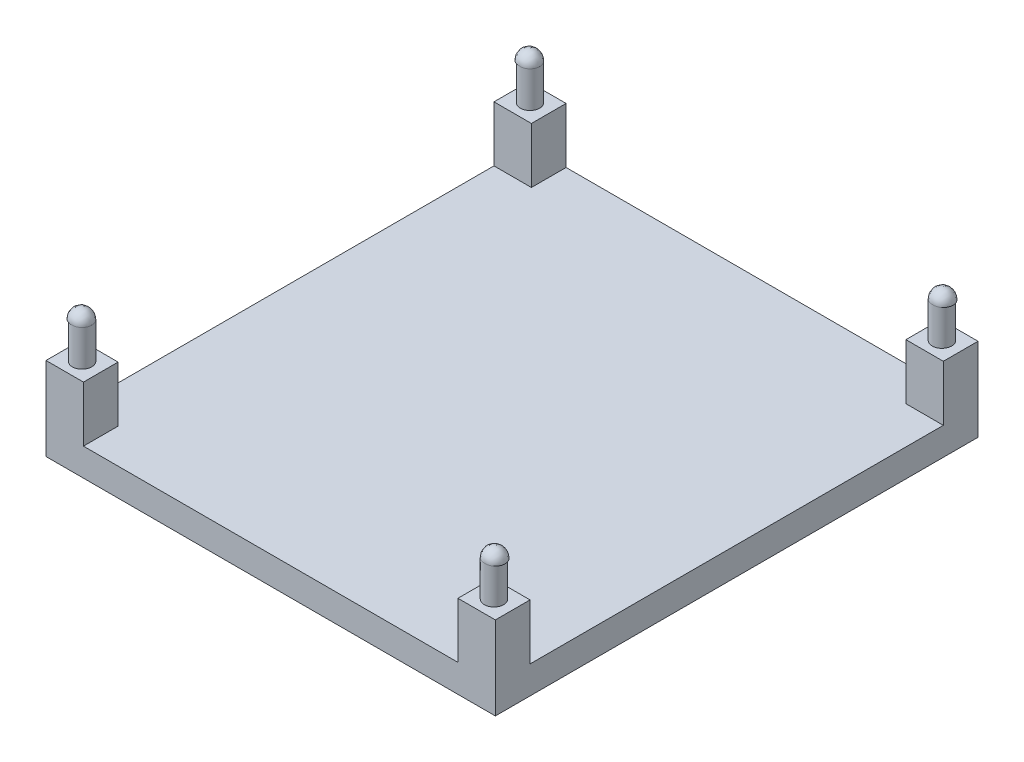
SolidWorks part; units mm, degrees
ref_plane "Front Plane" through (0, 0, 0) normal (0, 0, 1) x (1, 0, 0)
ref_plane "Top Plane" through (0, 0, 0) normal (0, 1, 0) x (1, 0, 0)
ref_plane "Right Plane" through (0, 0, 0) normal (1, 0, 0) x (0, 0, -1)
sketch "Sketch1" plane through (0, 0, 0) normal (0, 1, 0) x (1, 0, 0)
  line L0 (0, -44.45) -> (0, 44.45) construction
  line L1 (-41.275, 44.45) -> (41.275, 44.45)
  line L2 (-41.275, 44.45) -> (-41.275, -44.45)
  line L3 (-41.275, -44.45) -> (41.275, -44.45)
  line L4 (41.275, 44.45) -> (41.275, -44.45)
  line L5 (-41.275, 44.45) -> (41.275, -44.45) construction
  line L6 (-41.275, -44.45) -> (41.275, 44.45) construction
  line L7 (-41.275, 0) -> (41.275, 0) construction
  circle A0 centre (38.1, -41.275) radius 2.3812
  circle A1 centre (-38.1, -41.275) radius 2.3812
  circle A2 centre (38.1, 41.275) radius 2.3812
  circle A3 centre (-38.1, 41.275) radius 2.3812
  point P0 (0, 0)
  dimension "D3" = 76.2
  dimension "D5" = 38.1
  dimension "D6" = 3.175
  dimension "D1" = 88.9
  dimension "D2" = 82.55
  dimension "D4" = 82.55
sketch "Sketch2" plane through (0, 0, 0) normal (0, 1, 0) x (1, 0, 0)
  line L0 (0, -44.196) -> (0, 44.196) construction
  line L1 (-41.148, 44.196) -> (41.148, 44.196)
  line L2 (-41.148, 44.196) -> (-41.148, -44.196)
  line L3 (-41.148, -44.196) -> (41.148, -44.196)
  line L4 (41.148, 44.196) -> (41.148, -44.196)
  line L5 (-41.148, 44.196) -> (41.148, -44.196) construction
  line L6 (-41.148, -44.196) -> (41.148, 44.196) construction
  line L7 (-41.148, 0) -> (41.148, 0) construction
  circle A0 centre (37.719, -41.021) radius 1.778
  circle A1 centre (-37.719, -41.021) radius 1.778
  circle A2 centre (37.719, 41.021) radius 1.778
  circle A3 centre (-37.719, 41.021) radius 1.778
  point P0 (0, 0)
  dimension "D3" = 75.438
  dimension "D5" = 37.719
  dimension "D6" = 3.429
  dimension "D9" = 3.556
  dimension "D10" = 3.556
  dimension "D11" = 3.556
  dimension "D12" = 3.556
  dimension "D1" = 88.392
  dimension "D2" = 82.296
  dimension "D4" = 82.042
  dimension "D13" = 3.429
  dimension "D14" = 3.175
  dimension "D15" = 3.429
  dimension "D16" = 3.175
  dimension "D17" = 3.429
  dimension "D18" = 3.175
extrude "Boss-Extrude2" add sketch "Sketch2" along normal blind 21.844 contours A2 | A3 | A1 | A0
extrude "Boss-Extrude3" add sketch "Sketch2<4>" along normal blind 5.08 contours L2 L1 L4 L3
sketch "Sketch2<4>" plane through (0, 0, 0) normal (0, 1, 0) x (1, 0, 0) same geometry as "Sketch2"
sketch "Sketch4" plane through (0, 0, 0) normal (0, -1, 0) x (1, 0, 0)
  circle A0 centre (-41.148, 44.196) radius 3.2269
  circle A1 centre (41.148, 44.196) radius 3.175
  circle A2 centre (-41.148, -44.196) radius 3.175
  circle A3 centre (41.148, -44.196) radius 3.175
sketch "Sketch3" plane through (0, 21.844, 0) normal (0, 1, 0) x (1, 0, 0)
  line L0 (37.8457, -39.2475) -> (37.8457, -42.7945)
  circle A2 centre (37.719, -41.021) radius 1.778 construction
  arc A3 (37.8457, -39.2475) -> (37.8457, -42.7945) centre (37.9724, -41.021) cw
revolve "Revolve1" add sketch "Sketch3" angle 180 about L0
pattern_linear "LPattern1" count 2 spacing 75.692 along (-1, 0, 0) count 2 spacing 82.042 along (0, 0, -1) of "Revolve1"
sketch "Sketch5" plane through (0, 5.08, 0) normal (0, 1, 0) x (1, 0, 0)
  line L0 (0, 44.196) -> (0, -44.196) construction
  line L1 (-34.29, 37.846) -> (-41.148, 37.846)
  line L2 (-34.29, 37.846) -> (-34.29, 44.196)
  line L3 (-34.29, 44.196) -> (-41.148, 44.196)
  line L4 (-41.148, 37.846) -> (-41.148, 44.196)
  line L5 (-34.29, 37.846) -> (-41.148, 44.196) construction
  line L6 (-34.29, 44.196) -> (-41.148, 37.846) construction
  line L7 (-41.148, 44.196) -> (41.148, 44.196) construction
  line L12 (-41.148, -44.196) -> (41.148, -44.196) construction
  line L13 (34.29, -44.196) -> (41.148, -44.196)
  line L18 (-34.29, -44.196) -> (-41.148, -37.846) construction
  line L19 (-34.29, -37.846) -> (-41.148, -44.196) construction
  line L20 (-34.29, -44.196) -> (-34.29, -37.846)
  line L21 (-34.29, -44.196) -> (-41.148, -44.196)
  line L22 (-41.148, -44.196) -> (-41.148, -37.846)
  line L23 (-34.29, -37.846) -> (-41.148, -37.846)
  line L24 (41.402, 37.846) -> (41.402, 44.196) [skipped]
  line L25 (41.402, 37.846) -> (34.544, 37.846) [skipped]
  line L26 (34.544, 37.846) -> (34.544, 44.196) [skipped]
  line L27 (41.402, 44.196) -> (34.544, 44.196) [skipped]
  line L28 (41.402, 37.846) -> (34.544, 44.196) construction
  line L29 (41.402, 44.196) -> (34.544, 37.846) construction
  line L30 (41.402, -44.196) -> (41.402, -37.846) [skipped]
  line L31 (41.402, -44.196) -> (34.544, -44.196) [skipped]
  line L32 (34.544, -44.196) -> (34.544, -37.846) [skipped]
  line L33 (41.402, -37.846) -> (34.544, -37.846) [skipped]
  line L34 (41.402, -44.196) -> (34.544, -37.846) construction
  line L35 (41.402, -37.846) -> (34.544, -44.196) construction
  line L36 (41.148, -44.196) -> (41.148, -37.846)
  line L37 (34.29, -37.846) -> (41.148, -37.846)
  line L38 (34.29, -44.196) -> (34.29, -37.846)
  line L39 (34.29, 44.196) -> (41.148, 44.196)
  line L40 (41.148, 37.846) -> (41.148, 44.196)
  line L41 (34.29, 37.846) -> (41.148, 37.846)
  line L42 (34.29, 37.846) -> (34.29, 44.196)
  point P0 (-37.719, 41.021)
  point P5 (37.973, 41.021)
  point P6 (37.973, -41.021)
  point P22 (-37.719, -41.021)
  dimension "D1" = 6.35
  dimension "D2" = 6.858
  dimension "D3" = 2
  dimension "D4" = 2
extrude "Boss-Extrude4" add sketch "Sketch5" along normal blind 10.16
